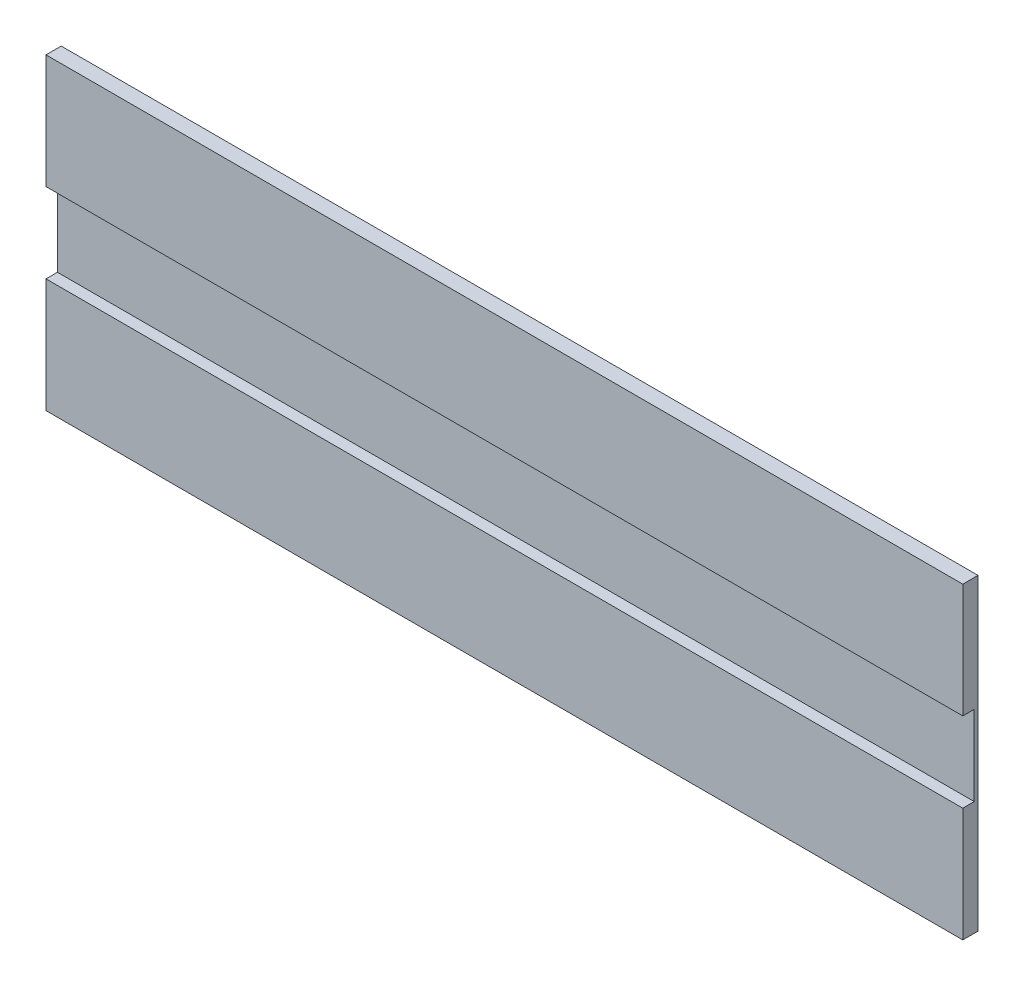
SolidWorks part; units mm, degrees
ref_plane "Ebene vorne" through (0, 0, 0) normal (0, 0, 1) x (1, 0, 0)
ref_plane "Ebene oben" through (0, 0, 0) normal (0, 1, 0) x (1, 0, 0)
ref_plane "Ebene rechts" through (0, 0, 0) normal (1, 0, 0) x (0, 0, -1)
sketch "Skizze1" plane through (0, 0, 0) normal (0, 0, 1) x (1, 0, 0)
  line L1 (0, 0) -> (12050, 0)
  line L2 (0, 0) -> (0, 4050)
  line L3 (0, 4050) -> (12050, 4050)
  line L4 (12050, 0) -> (12050, 4050)
  dimension "D1" = 12050
  dimension "D2" = 4050
extrude "Aufsatz-Linear austragen1" add sketch "Skizze1" along normal blind 200
sketch "Skizze2" plane through (12050, 0, 0) normal (1, 0, 0) x (0, 0, -1)
  line L0 (-200, 0) -> (-200, 4050) construction
  line L1 (-200, 2550) -> (-50, 2550)
  line L2 (-200, 2550) -> (-200, 1500)
  line L3 (-200, 1500) -> (-50, 1500)
  line L4 (-50, 2550) -> (-50, 1500)
  line L5 (-200, 4050) -> (0, 4050) construction
  dimension "D1" = 1500
  dimension "D2" = 1500
  dimension "D3" = 150
extrude "Schnitt-Linear austragen1" cut sketch "Skizze2" against normal through all
